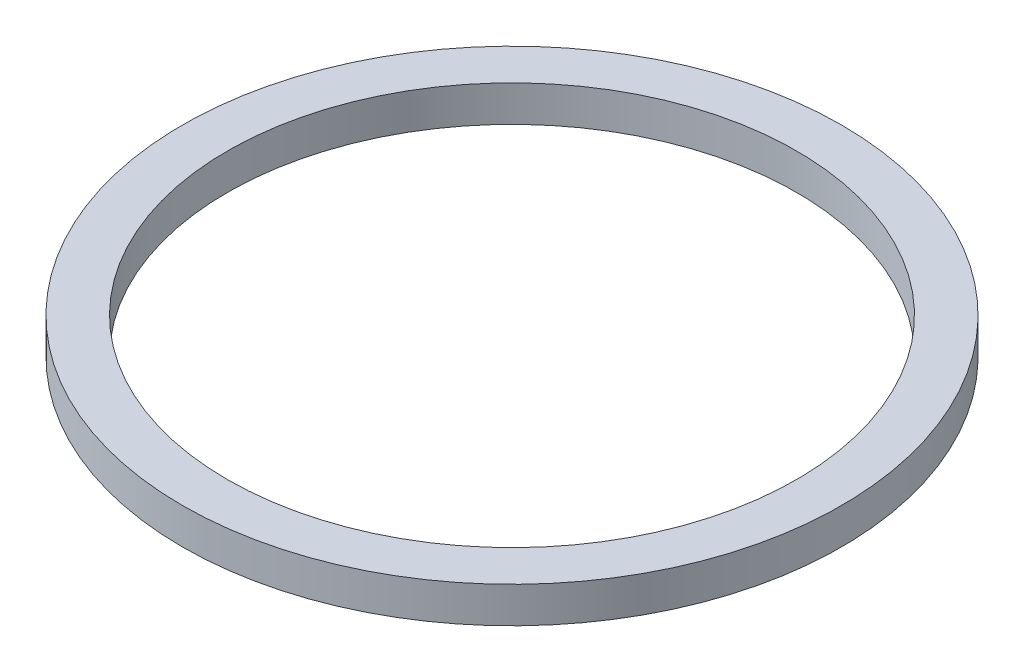
SolidWorks part; units mm, degrees
ref_plane "Front Plane" through (0, 0, 0) normal (0, 0, 1) x (1, 0, 0)
ref_plane "Top Plane" through (0, 0, 0) normal (0, 1, 0) x (1, 0, 0)
ref_plane "Right Plane" through (0, 0, 0) normal (1, 0, 0) x (0, 0, -1)
sketch "Sketch1" plane through (0, 0, 0) normal (0, 1, 0) x (1, 0, 0)
  circle A0 centre (0, 0) radius 55
  dimension "FLANGE_OD" = 110
extrude "Boss-Extrude1" add sketch "Sketch1" along normal blind 6
sketch "Sketch2" plane through (0, 0, 0) normal (0, 1, 0) x (1, 0, 0)
  circle A0 centre (0, 0) radius 47.5
  dimension "BORE_D" = 95
extrude "Cut-Extrude1" cut sketch "Sketch2" along normal through all
sketch "Sketch3" plane through (0, 6, 0) normal (0, 1, 0) x (1, 0, 0)
  circle A0 centre (0, 0) radius 25.1023 construction
  circle A1 centre (-25.1023, 0) radius 1.5
  dimension "BOLT_D" = 3
  dimension "BOLT_PCD" = 50.2047
extrude "Cut-Extrude2" cut sketch "Sketch3" against normal blind 4.2905 rebuild error yes
pattern_circular "CirPattern1" count 3 over 360 rebuild error yes
